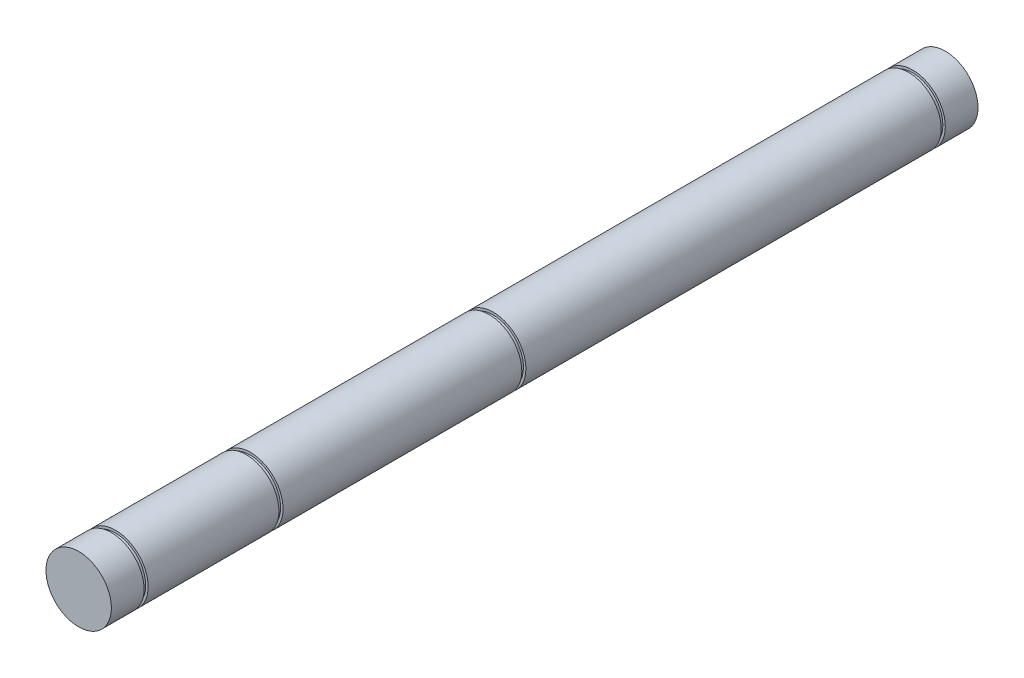
SolidWorks part; units mm, degrees
ref_plane "Alzado" through (0, 0, 0) normal (0, 0, 1) x (1, 0, 0)
ref_plane "Planta" through (0, 0, 0) normal (0, 1, 0) x (1, 0, 0)
ref_plane "Vista lateral" through (0, 0, 0) normal (1, 0, 0) x (0, 0, -1)
sketch "Croquis1" plane through (0, 0, 0) normal (0, 0, 1) x (1, 0, 0)
  circle A0 centre (0, 0) radius 2
  dimension "D1" = 4
extrude "Saliente-Extruir1" add sketch "Croquis1" along normal blind 53
sketch "Croquis2" plane through (0, 0, 0) normal (1, 0, 0) x (0, 0, -1)
  line L0 (0, 0) -> (-53, 0) construction
  line L5 (0, -2) -> (0, 2) construction
  line L6 (-53, 2) -> (-53, -2) construction
  line L7 (0, 2) -> (0, -2.0027) construction
  line L8 (-26.5, 0) -> (-26.5, -2) construction
  line L9 (-50.75, 3.85) -> (-50.75, 1.85)
  line L10 (-51, 1.85) -> (-50.75, 1.85)
  line L11 (-51, 3.85) -> (-51, 1.85)
  line L12 (-51, 3.85) -> (-50.75, 3.85)
  line L13 (-50.75, 1.85) -> (-42.75, 1.85) construction
  line L18 (-42.5, 3.85) -> (-42.75, 3.85)
  line L19 (-42.5, 3.85) -> (-42.5, 1.85)
  line L20 (-42.5, 1.85) -> (-42.75, 1.85)
  line L21 (-42.75, 3.85) -> (-42.75, 1.85)
  line L22 (-53, -2) -> (0, -2) construction
  line L23 (-2, 1.85) -> (-2.25, 1.85)
  line L24 (-27.9, 1.85) -> (-27.65, 1.85)
  line L25 (-27.65, 3.85) -> (-27.65, 1.85)
  line L26 (-27.9, 3.85) -> (-27.9, 1.85)
  line L27 (-27.9, 3.85) -> (-27.65, 3.85)
  line L28 (-2, 3.85) -> (-2.25, 3.85)
  line L29 (-2, 3.85) -> (-2, 1.85)
  line L30 (-2.25, 3.85) -> (-2.25, 1.85)
  dimension "D1" = 2
  dimension "D2" = 0.25
  dimension "D3" = 8
  dimension "D4" = 1.85
  dimension "D5" = 0.25
  dimension "D6" = 2
  dimension "D7" = 2
  dimension "D8" = 2
  dimension "D9" = 25.4
  dimension "D10" = 0.25
revolve "Cortar-Revolución1" cut sketch "Croquis2" angle 360 about L0
